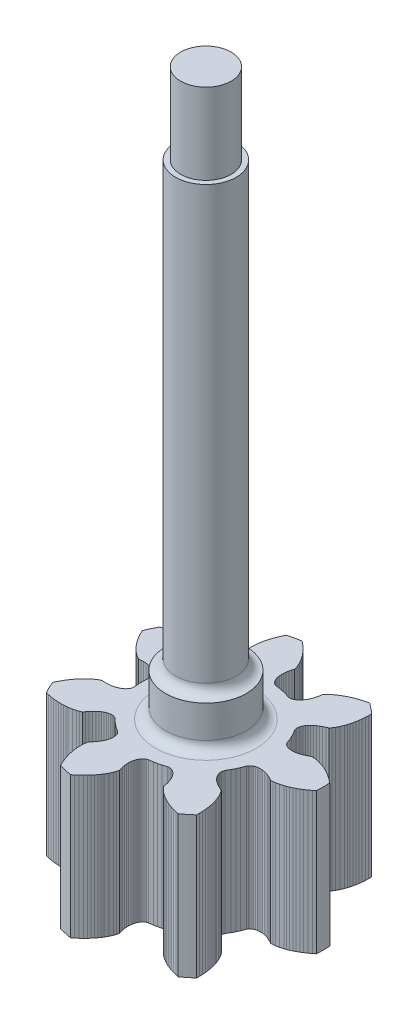
SolidWorks part; units mm, degrees
ref_plane "Front Plane" through (0, 0, 0) normal (0, 0, 1) x (1, 0, 0)
ref_plane "Top Plane" through (0, 0, 0) normal (0, 1, 0) x (1, 0, 0)
ref_plane "Right Plane" through (0, 0, 0) normal (1, 0, 0) x (0, 0, -1)
sketch "Sketch1" plane through (0, 0, 0) normal (0, 1, 0) x (1, 0, 0)
  circle A0 centre (0, 0) radius 2
  dimension "D1" = 4
extrude "Boss-Extrude1" add sketch "Sketch1" along normal blind 2.1
sketch "Sketch2" plane through (0, 2.1, 0) normal (0, 1, 0) x (1, 0, 0)
  circle A0 centre (0, 0) radius 1.5
  dimension "D1" = 3
extrude "Boss-Extrude3" add sketch "Sketch2" along normal blind 25.9
sketch "Sketch4" plane through (0, 0, 0) normal (0, -1, 0) x (1, 0, 0)
  line L420 (-1.6777, -5.4575) -> (-1.7402, -5.3144)
  line L421 (-1.7402, -5.3144) -> (-1.7939, -5.1757)
  line L422 (-1.7939, -5.1757) -> (-1.8392, -5.0423)
  line L423 (-1.8392, -5.0423) -> (-1.8764, -4.916)
  line L424 (-1.8764, -4.916) -> (-1.9071, -4.7932)
  line L425 (-1.9071, -4.7932) -> (-1.9311, -4.676)
  line L426 (-1.9311, -4.676) -> (-1.9488, -4.5668)
  line L427 (-1.9488, -4.5668) -> (-1.961, -4.464)
  line L428 (-1.961, -4.464) -> (-1.9715, -4.2798)
  line L429 (-1.9715, -4.2798) -> (-1.9674, -4.1246)
  line L430 (-1.9674, -4.1246) -> (-1.9537, -4.0009)
  line L431 (-1.9537, -4.0009) -> (-1.9303, -3.8867)
  line L432 (-1.9303, -3.8867) -> (-1.8594, -3.8097)
  line L433 (-1.8594, -3.8097) -> (-1.7784, -3.7125)
  line L434 (-1.7784, -3.7125) -> (-1.7087, -3.6155)
  line L435 (-1.7087, -3.6155) -> (-1.6501, -3.5195)
  line L436 (-1.6501, -3.5195) -> (-1.6023, -3.4251)
  line L437 (-1.6023, -3.4251) -> (-1.5652, -3.3333)
  line L438 (-1.5652, -3.3333) -> (-1.5384, -3.2446)
  line L439 (-1.5384, -3.2446) -> (-1.5215, -3.1597)
  line L440 (-1.5215, -3.1597) -> (-1.5143, -3.0795)
  line L441 (-1.5143, -3.0795) -> (-1.5162, -3.0043)
  line L442 (-1.5162, -3.0043) -> (-1.5269, -2.935)
  line L443 (-1.5269, -2.935) -> (-1.5457, -2.8721)
  line L444 (-1.5457, -2.8721) -> (-1.5723, -2.8162)
  line L445 (-1.5723, -2.8162) -> (-1.606, -2.7677)
  line L446 (-1.606, -2.7677) -> (-1.6572, -2.7183)
  line L447 (-1.6572, -2.7183) -> (-1.8447, -2.5928)
  line L448 (-1.8447, -2.5928) -> (-1.984, -2.4878)
  line L449 (-1.984, -2.4878) -> (-2.1173, -2.3754)
  line L450 (-2.1173, -2.3754) -> (-2.2814, -2.2205)
  line L451 (-2.2814, -2.2205) -> (-2.341, -2.1815)
  line L452 (-2.341, -2.1815) -> (-2.3957, -2.1595)
  line L453 (-2.3957, -2.1595) -> (-2.4562, -2.146)
  line L454 (-2.4562, -2.146) -> (-2.5217, -2.1417)
  line L455 (-2.5217, -2.1417) -> (-2.5917, -2.1467)
  line L456 (-2.5917, -2.1467) -> (-2.6653, -2.1615)
  line L457 (-2.6653, -2.1615) -> (-2.742, -2.1865)
  line L458 (-2.742, -2.1865) -> (-2.8209, -2.2218)
  line L459 (-2.8209, -2.2218) -> (-2.9014, -2.2676)
  line L460 (-2.9014, -2.2676) -> (-2.9827, -2.3243)
  line L461 (-2.9827, -2.3243) -> (-3.0641, -2.3918)
  line L462 (-3.0641, -2.3918) -> (-3.1447, -2.4703)
  line L463 (-3.1447, -2.4703) -> (-3.2237, -2.5599)
  line L464 (-3.2237, -2.5599) -> (-3.3005, -2.6605)
  line L465 (-3.3005, -2.6605) -> (-3.3598, -2.7467)
  line L466 (-3.3598, -2.7467) -> (-3.4659, -2.795)
  line L467 (-3.4659, -2.795) -> (-3.5835, -2.8358)
  line L468 (-3.5835, -2.8358) -> (-3.7338, -2.8744)
  line L469 (-3.7338, -2.8744) -> (-3.9158, -2.9052)
  line L470 (-3.9158, -2.9052) -> (-4.0187, -2.9161)
  line L471 (-4.0187, -2.9161) -> (-4.1291, -2.9232)
  line L472 (-4.1291, -2.9232) -> (-4.2487, -2.9258)
  line L473 (-4.2487, -2.9258) -> (-4.3752, -2.9233)
  line L474 (-4.3752, -2.9233) -> (-4.5067, -2.9151)
  line L475 (-4.5067, -2.9151) -> (-4.6468, -2.9006)
  line L476 (-4.6468, -2.9006) -> (-4.794, -2.8791)
  line L477 (-4.794, -2.8791) -> (-4.9474, -2.85)
  line L478 (-4.9474, -2.85) -> (-5.0902, -2.8167)
  line L479 (-5.3759, -2.2235) -> (-5.3129, -2.0911)
  line L480 (-5.3129, -2.0911) -> (-5.2399, -1.953)
  line L481 (-5.2399, -1.953) -> (-5.165, -1.8245)
  line L482 (-5.165, -1.8245) -> (-5.089, -1.7059)
  line L483 (-5.089, -1.7059) -> (-5.0134, -1.5981)
  line L484 (-5.0134, -1.5981) -> (-4.9365, -1.4976)
  line L485 (-4.9365, -1.4976) -> (-4.8599, -1.4057)
  line L486 (-4.8599, -1.4057) -> (-4.7855, -1.3238)
  line L487 (-4.7855, -1.3238) -> (-4.7128, -1.2502)
  line L488 (-4.7128, -1.2502) -> (-4.5753, -1.1271)
  line L489 (-4.5753, -1.1271) -> (-4.4514, -1.0336)
  line L490 (-4.4514, -1.0336) -> (-4.3462, -0.9671)
  line L491 (-4.3462, -0.9671) -> (-4.2422, -0.9142)
  line L492 (-4.2422, -0.9142) -> (-4.1379, -0.9217)
  line L493 (-4.1379, -0.9217) -> (-4.0114, -0.9244)
  line L494 (-4.0114, -0.9244) -> (-3.8921, -0.9184)
  line L495 (-3.8921, -0.9184) -> (-3.7804, -0.9043)
  line L496 (-3.7804, -0.9043) -> (-3.6769, -0.8828)
  line L497 (-3.6769, -0.8828) -> (-3.5819, -0.8546)
  line L498 (-3.5819, -0.8546) -> (-3.4959, -0.8203)
  line L499 (-3.4959, -0.8203) -> (-3.4191, -0.7805)
  line L500 (-3.4191, -0.7805) -> (-3.3518, -0.7361)
  line L501 (-3.3518, -0.7361) -> (-3.2942, -0.6878)
  line L502 (-3.2942, -0.6878) -> (-3.2467, -0.6363)
  line L503 (-3.2467, -0.6363) -> (-3.2093, -0.5823)
  line L504 (-3.2093, -0.5823) -> (-3.1821, -0.5267)
  line L505 (-3.1821, -0.5267) -> (-3.1652, -0.4701)
  line L506 (-3.1652, -0.4701) -> (-3.1585, -0.3992)
  line L507 (-3.1585, -0.3992) -> (-3.1773, -0.1744)
  line L508 (-3.1773, -0.1744) -> (-3.1821, 0)
  line L509 (-3.1821, 0) -> (-3.1773, 0.1743)
  line L510 (-3.1773, 0.1743) -> (-3.1585, 0.3991)
  line L511 (-3.1585, 0.3991) -> (-3.1652, 0.47)
  line L512 (-3.1652, 0.47) -> (-3.1821, 0.5266)
  line L513 (-3.1821, 0.5266) -> (-3.2093, 0.5822)
  line L514 (-3.2093, 0.5822) -> (-3.2467, 0.6362)
  line L515 (-3.2467, 0.6362) -> (-3.2942, 0.6877)
  line L516 (-3.2942, 0.6877) -> (-3.3518, 0.7361)
  line L517 (-3.3518, 0.7361) -> (-3.4191, 0.7805)
  line L518 (-3.4191, 0.7805) -> (-3.4959, 0.8202)
  line L519 (-3.4959, 0.8202) -> (-3.5819, 0.8545)
  line L520 (-3.5819, 0.8545) -> (-3.6769, 0.8828)
  line L521 (-3.6769, 0.8828) -> (-3.7804, 0.9043)
  line L522 (-3.7804, 0.9043) -> (-3.8921, 0.9183)
  line L523 (-3.8921, 0.9183) -> (-4.0114, 0.9243)
  line L524 (-4.0114, 0.9243) -> (-4.1379, 0.9216)
  line L525 (-4.1379, 0.9216) -> (-4.2422, 0.9142)
  line L526 (-4.2422, 0.9142) -> (-4.3462, 0.967)
  line L527 (-4.3462, 0.967) -> (-4.4514, 1.0335)
  line L528 (-4.4514, 1.0335) -> (-4.5753, 1.127)
  line L529 (-4.5753, 1.127) -> (-4.7128, 1.2501)
  line L530 (-4.7128, 1.2501) -> (-4.7855, 1.3238)
  line L531 (-4.7855, 1.3238) -> (-4.8599, 1.4056)
  line L532 (-4.8599, 1.4056) -> (-4.9365, 1.4975)
  line L533 (-4.9365, 1.4975) -> (-5.0134, 1.598)
  line L534 (-5.0134, 1.598) -> (-5.089, 1.7059)
  line L535 (-5.089, 1.7059) -> (-5.165, 1.8244)
  line L536 (-5.165, 1.8244) -> (-5.2399, 1.9529)
  line L537 (-5.2399, 1.9529) -> (-5.3129, 2.0911)
  line L538 (-5.3129, 2.0911) -> (-5.3759, 2.2234)
  line L539 (-5.0902, 2.8167) -> (-4.9474, 2.8499)
  line L540 (-4.9474, 2.8499) -> (-4.794, 2.879)
  line L541 (-4.794, 2.879) -> (-4.6468, 2.9005)
  line L542 (-4.6468, 2.9005) -> (-4.5067, 2.9151)
  line L543 (-4.5067, 2.9151) -> (-4.3752, 2.9232)
  line L544 (-4.3752, 2.9232) -> (-4.2487, 2.9257)
  line L545 (-4.2487, 2.9257) -> (-4.1291, 2.9231)
  line L546 (-4.1291, 2.9231) -> (-4.0187, 2.916)
  line L547 (-4.0187, 2.916) -> (-3.9158, 2.9051)
  line L548 (-3.9158, 2.9051) -> (-3.7338, 2.8743)
  line L549 (-3.7338, 2.8743) -> (-3.5835, 2.8358)
  line L550 (-3.5835, 2.8358) -> (-3.4659, 2.7949)
  line L551 (-3.4659, 2.7949) -> (-3.3598, 2.7466)
  line L552 (-3.3598, 2.7466) -> (-3.3005, 2.6604)
  line L553 (-3.3005, 2.6604) -> (-3.2237, 2.5598)
  line L554 (-3.2237, 2.5598) -> (-3.1447, 2.4703)
  line L555 (-3.1447, 2.4703) -> (-3.0641, 2.3918)
  line L556 (-3.0641, 2.3918) -> (-2.9827, 2.3242)
  line L557 (-2.9827, 2.3242) -> (-2.9014, 2.2676)
  line L558 (-2.9014, 2.2676) -> (-2.8209, 2.2217)
  line L559 (-2.8209, 2.2217) -> (-2.742, 2.1864)
  line L560 (-2.742, 2.1864) -> (-2.6653, 2.1615)
  line L561 (-2.6653, 2.1615) -> (-2.5917, 2.1466)
  line L562 (-2.5917, 2.1466) -> (-2.5217, 2.1416)
  line L563 (-2.5217, 2.1416) -> (-2.4562, 2.146)
  line L564 (-2.4562, 2.146) -> (-2.3957, 2.1594)
  line L565 (-2.3957, 2.1594) -> (-2.341, 2.1815)
  line L566 (-2.341, 2.1815) -> (-2.2814, 2.2205)
  line L567 (-2.2814, 2.2205) -> (-2.1173, 2.3753)
  line L568 (-2.1173, 2.3753) -> (-1.984, 2.4878)
  line L569 (-1.984, 2.4878) -> (-1.8447, 2.5927)
  line L570 (-1.8447, 2.5927) -> (-1.6572, 2.7182)
  line L571 (-1.6572, 2.7182) -> (-1.606, 2.7676)
  line L572 (-1.606, 2.7676) -> (-1.5723, 2.8161)
  line L573 (-1.5723, 2.8161) -> (-1.5457, 2.8721)
  line L574 (-1.5457, 2.8721) -> (-1.5269, 2.935)
  line L575 (-1.5269, 2.935) -> (-1.5162, 3.0043)
  line L576 (-1.5162, 3.0043) -> (-1.5143, 3.0794)
  line L577 (-1.5143, 3.0794) -> (-1.5215, 3.1597)
  line L578 (-1.5215, 3.1597) -> (-1.5384, 3.2445)
  line L579 (-1.5384, 3.2445) -> (-1.5652, 3.3332)
  line L580 (-1.5652, 3.3332) -> (-1.6023, 3.4251)
  line L581 (-1.6023, 3.4251) -> (-1.6501, 3.5194)
  line L582 (-1.6501, 3.5194) -> (-1.7087, 3.6154)
  line L583 (-1.7087, 3.6154) -> (-1.7784, 3.7125)
  line L584 (-1.7784, 3.7125) -> (-1.8594, 3.8097)
  line L585 (-1.8594, 3.8097) -> (-1.9303, 3.8866)
  line L586 (-1.9303, 3.8866) -> (-1.9537, 4.0009)
  line L587 (-1.9537, 4.0009) -> (-1.9674, 4.1246)
  line L588 (-1.9674, 4.1246) -> (-1.9715, 4.2797)
  line L589 (-1.9715, 4.2797) -> (-1.961, 4.464)
  line L590 (-1.961, 4.464) -> (-1.9488, 4.5668)
  line L591 (-1.9488, 4.5668) -> (-1.9311, 4.6759)
  line L592 (-1.9311, 4.6759) -> (-1.9071, 4.7932)
  line L593 (-1.9071, 4.7932) -> (-1.8764, 4.9159)
  line L594 (-1.8764, 4.9159) -> (-1.8392, 5.0423)
  line L595 (-1.8392, 5.0423) -> (-1.7939, 5.1756)
  line L596 (-1.7939, 5.1756) -> (-1.7402, 5.3143)
  line L597 (-1.7402, 5.3143) -> (-1.6777, 5.4575)
  line L598 (-1.6777, 5.4575) -> (-1.6135, 5.5893)
  line L599 (-0.9715, 5.7358) -> (-0.8565, 5.6449)
  line L600 (-0.8565, 5.6449) -> (-0.7381, 5.543)
  line L601 (-0.7381, 5.543) -> (-0.6295, 5.4414)
  line L602 (-0.6295, 5.4414) -> (-0.5308, 5.3409)
  line L603 (-0.5308, 5.3409) -> (-0.4425, 5.2432)
  line L604 (-0.4425, 5.2432) -> (-0.3616, 5.1459)
  line L605 (-0.3616, 5.1459) -> (-0.2891, 5.0507)
  line L606 (-0.2891, 5.0507) -> (-0.2258, 4.96)
  line L607 (-0.2258, 4.96) -> (-0.1702, 4.8727)
  line L608 (-0.1702, 4.8727) -> (-0.0808, 4.7113)
  line L609 (-0.0808, 4.7113) -> (-0.0172, 4.5697)
  line L610 (-0.0172, 4.5697) -> (0.0242, 4.4523)
  line L611 (0.0242, 4.4523) -> (0.0526, 4.3392)
  line L612 (0.0526, 4.3392) -> (0.0222, 4.2391)
  line L613 (0.0222, 4.2391) -> (-0.0086, 4.1164)
  line L614 (-0.0086, 4.1164) -> (-0.0293, 3.9987)
  line L615 (-0.0293, 3.9987) -> (-0.0405, 3.8868)
  line L616 (-0.0405, 3.8868) -> (-0.0426, 3.7811)
  line L617 (-0.0426, 3.7811) -> (-0.0362, 3.6822)
  line L618 (-0.0362, 3.6822) -> (-0.0218, 3.5907)
  line L619 (-0.0218, 3.5907) -> (-0.0002, 3.5069)
  line L620 (-0.0002, 3.5069) -> (0.0281, 3.4314)
  line L621 (0.0281, 3.4314) -> (0.0624, 3.3646)
  line L622 (0.0624, 3.3646) -> (0.1021, 3.3068)
  line L623 (0.1021, 3.3068) -> (0.1464, 3.2583)
  line L624 (0.1464, 3.2583) -> (0.1946, 3.2194)
  line L625 (0.1946, 3.2194) -> (0.246, 3.1903)
  line L626 (0.246, 3.1903) -> (0.3136, 3.1681)
  line L627 (0.3136, 3.1681) -> (0.537, 3.1363)
  line L628 (0.537, 3.1363) -> (0.708, 3.1022)
  line L629 (0.708, 3.1022) -> (0.8769, 3.0588)
  line L630 (0.8769, 3.0588) -> (1.0919, 2.9904)
  line L631 (1.0919, 2.9904) -> (1.1625, 2.9811)
  line L632 (1.1625, 2.9811) -> (1.2214, 2.985)
  line L633 (1.2214, 2.985) -> (1.2817, 2.9991)
  line L634 (1.2817, 2.9991) -> (1.3427, 3.0236)
  line L635 (1.3427, 3.0236) -> (1.4035, 3.0585)
  line L636 (1.4035, 3.0585) -> (1.4634, 3.1038)
  line L637 (1.4634, 3.1038) -> (1.5217, 3.1596)
  line L638 (1.5217, 3.1596) -> (1.5775, 3.2256)
  line L639 (1.5775, 3.2256) -> (1.6301, 3.3019)
  line L640 (1.6301, 3.3019) -> (1.6788, 3.3882)
  line L641 (1.6788, 3.3882) -> (1.7228, 3.4843)
  line L642 (1.7228, 3.4843) -> (1.7613, 3.59)
  line L643 (1.7613, 3.59) -> (1.7937, 3.705)
  line L644 (1.7937, 3.705) -> (1.8192, 3.829)
  line L645 (1.8192, 3.829) -> (1.8352, 3.9324)
  line L646 (1.8352, 3.9324) -> (1.9099, 4.0219)
  line L647 (1.9099, 4.0219) -> (1.9981, 4.1097)
  line L648 (1.9981, 4.1097) -> (2.1168, 4.2097)
  line L649 (2.1168, 4.2097) -> (2.2674, 4.3164)
  line L650 (2.2674, 4.3164) -> (2.3554, 4.3709)
  line L651 (2.3554, 4.3709) -> (2.4518, 4.4251)
  line L652 (2.4518, 4.4251) -> (2.5584, 4.4794)
  line L653 (2.5584, 4.4794) -> (2.6735, 4.532)
  line L654 (2.6735, 4.532) -> (2.7955, 4.5817)
  line L655 (2.7955, 4.5817) -> (2.928, 4.6294)
  line L656 (2.928, 4.6294) -> (3.0699, 4.6739)
  line L657 (3.0699, 4.6739) -> (3.2208, 4.7143)
  line L658 (3.2208, 4.7143) -> (3.3639, 4.7463)
  line L659 (3.8787, 4.3357) -> (3.8793, 4.1891)
  line L660 (3.8793, 4.1891) -> (3.8735, 4.033)
  line L661 (3.8735, 4.033) -> (3.8618, 3.8847)
  line L662 (3.8618, 3.8847) -> (3.8448, 3.7449)
  line L663 (3.8448, 3.7449) -> (3.8234, 3.615)
  line L664 (3.8234, 3.615) -> (3.7978, 3.4911)
  line L665 (3.7978, 3.4911) -> (3.7686, 3.375)
  line L666 (3.7686, 3.375) -> (3.7371, 3.269)
  line L667 (3.7371, 3.269) -> (3.7036, 3.1711)
  line L668 (3.7036, 3.1711) -> (3.6331, 3.0005)
  line L669 (3.6331, 3.0005) -> (3.562, 2.8625)
  line L670 (3.562, 2.8625) -> (3.4961, 2.757)
  line L671 (3.4961, 2.757) -> (3.4253, 2.6643)
  line L672 (3.4253, 2.6643) -> (3.3281, 2.6257)
  line L673 (3.3281, 2.6257) -> (3.213, 2.5732)
  line L674 (3.213, 2.5732) -> (3.1081, 2.516)
  line L675 (3.1081, 2.516) -> (3.0136, 2.4549)
  line L676 (3.0136, 2.4549) -> (2.9296, 2.3907)
  line L677 (2.9296, 2.3907) -> (2.8563, 2.324)
  line L678 (2.8563, 2.324) -> (2.7937, 2.2557)
  line L679 (2.7937, 2.2557) -> (2.7417, 2.1866)
  line L680 (2.7417, 2.1866) -> (2.7003, 2.1174)
  line L681 (2.7003, 2.1174) -> (2.6695, 2.0489)
  line L682 (2.6695, 2.0489) -> (2.649, 1.9819)
  line L683 (2.649, 1.9819) -> (2.6387, 1.917)
  line L684 (2.6387, 1.917) -> (2.6383, 1.8551)
  line L685 (2.6383, 1.8551) -> (2.6476, 1.7967)
  line L686 (2.6476, 1.7967) -> (2.6724, 1.73)
  line L687 (2.6724, 1.73) -> (2.7869, 1.5356)
  line L688 (2.7869, 1.5356) -> (2.8668, 1.3806)
  line L689 (2.8668, 1.3806) -> (2.9382, 1.2215)
  line L690 (2.9382, 1.2215) -> (3.0188, 1.0107)
  line L691 (3.0188, 1.0107) -> (3.0555, 0.9498)
  line L692 (3.0555, 0.9498) -> (3.0953, 0.9061)
  line L693 (3.0953, 0.9061) -> (3.144, 0.8678)
  line L694 (3.144, 0.8678) -> (3.2011, 0.8354)
  line L695 (3.2011, 0.8354) -> (3.2663, 0.8096)
  line L696 (3.2663, 0.8096) -> (3.3391, 0.791)
  line L697 (3.3391, 0.791) -> (3.419, 0.7802)
  line L698 (3.419, 0.7802) -> (3.5054, 0.7777)
  line L699 (3.5054, 0.7777) -> (3.5979, 0.7842)
  line L700 (3.5979, 0.7842) -> (3.6957, 0.7999)
  line L701 (3.6957, 0.7999) -> (3.7983, 0.8255)
  line L702 (3.7983, 0.8255) -> (3.905, 0.8612)
  line L703 (3.905, 0.8612) -> (4.0151, 0.9076)
  line L704 (4.0151, 0.9076) -> (4.1279, 0.9649)
  line L705 (4.1279, 0.9649) -> (4.2187, 1.0169)
  line L706 (4.2187, 1.0169) -> (4.3353, 1.0144)
  line L707 (4.3353, 1.0144) -> (4.4589, 1.0001)
  line L708 (4.4589, 1.0001) -> (4.6111, 0.9696)
  line L709 (4.6111, 0.9696) -> (4.7884, 0.9184)
  line L710 (4.7884, 0.9184) -> (4.8859, 0.8836)
  line L711 (4.8859, 0.8836) -> (4.9884, 0.8421)
  line L712 (4.9884, 0.8421) -> (5.0973, 0.7926)
  line L713 (5.0973, 0.7926) -> (5.2102, 0.7354)
  line L714 (5.2102, 0.7354) -> (5.3251, 0.671)
  line L715 (5.3251, 0.671) -> (5.445, 0.5972)
  line L716 (5.445, 0.5972) -> (5.5683, 0.5139)
  line L717 (5.5683, 0.5139) -> (5.6939, 0.4211)
  line L718 (5.6939, 0.4211) -> (5.8081, 0.3292)
  line L719 (5.8081, -0.3293) -> (5.6939, -0.4212)
  line L720 (5.6939, -0.4212) -> (5.5683, -0.514)
  line L721 (5.5683, -0.514) -> (5.445, -0.5972)
  line L722 (5.445, -0.5972) -> (5.3251, -0.6711)
  line L723 (5.3251, -0.6711) -> (5.2102, -0.7354)
  line L724 (5.2102, -0.7354) -> (5.0973, -0.7926)
  line L725 (5.0973, -0.7926) -> (4.9884, -0.8421)
  line L726 (4.9884, -0.8421) -> (4.8859, -0.8837)
  line L727 (4.8859, -0.8837) -> (4.7884, -0.9185)
  line L728 (4.7884, -0.9185) -> (4.6111, -0.9697)
  line L729 (4.6111, -0.9697) -> (4.4589, -1.0002)
  line L730 (4.4589, -1.0002) -> (4.3353, -1.0144)
  line L731 (4.3353, -1.0144) -> (4.2187, -1.017)
  line L732 (4.2187, -1.017) -> (4.1279, -0.965)
  line L733 (4.1279, -0.965) -> (4.0151, -0.9077)
  line L734 (4.0151, -0.9077) -> (3.905, -0.8613)
  line L735 (3.905, -0.8613) -> (3.7983, -0.8255)
  line L736 (3.7983, -0.8255) -> (3.6957, -0.8)
  line L737 (3.6957, -0.8) -> (3.5979, -0.7842)
  line L738 (3.5979, -0.7842) -> (3.5054, -0.7778)
  line L739 (3.5054, -0.7778) -> (3.419, -0.7803)
  line L740 (3.419, -0.7803) -> (3.3391, -0.7911)
  line L741 (3.3391, -0.7911) -> (3.2663, -0.8097)
  line L742 (3.2663, -0.8097) -> (3.2011, -0.8354)
  line L743 (3.2011, -0.8354) -> (3.144, -0.8678)
  line L744 (3.144, -0.8678) -> (3.0953, -0.9062)
  line L745 (3.0953, -0.9062) -> (3.0555, -0.9498)
  line L746 (3.0555, -0.9498) -> (3.0188, -1.0108)
  line L747 (3.0188, -1.0108) -> (2.9382, -1.2215)
  line L748 (2.9382, -1.2215) -> (2.8668, -1.3806)
  line L749 (2.8668, -1.3806) -> (2.7869, -1.5356)
  line L750 (2.7869, -1.5356) -> (2.6724, -1.7301)
  line L751 (2.6724, -1.7301) -> (2.6476, -1.7968)
  line L752 (2.6476, -1.7968) -> (2.6383, -1.8551)
  line L753 (2.6383, -1.8551) -> (2.6387, -1.9171)
  line L754 (2.6387, -1.9171) -> (2.649, -1.9819)
  line L755 (2.649, -1.9819) -> (2.6695, -2.049)
  line L756 (2.6695, -2.049) -> (2.7003, -2.1175)
  line L757 (2.7003, -2.1175) -> (2.7417, -2.1867)
  line L758 (2.7417, -2.1867) -> (2.7937, -2.2558)
  line L759 (2.7937, -2.2558) -> (2.8563, -2.3241)
  line L760 (2.8563, -2.3241) -> (2.9296, -2.3907)
  line L761 (2.9296, -2.3907) -> (3.0136, -2.455)
  line L762 (3.0136, -2.455) -> (3.1081, -2.5161)
  line L763 (3.1081, -2.5161) -> (3.213, -2.5733)
  line L764 (3.213, -2.5733) -> (3.3281, -2.6257)
  line L765 (3.3281, -2.6257) -> (3.4253, -2.6643)
  line L766 (3.4253, -2.6643) -> (3.4961, -2.757)
  line L767 (3.4961, -2.757) -> (3.562, -2.8626)
  line L768 (3.562, -2.8626) -> (3.6331, -3.0006)
  line L769 (3.6331, -3.0006) -> (3.7036, -3.1711)
  line L770 (3.7036, -3.1711) -> (3.7371, -3.2691)
  line L771 (3.7371, -3.2691) -> (3.7686, -3.3751)
  line L772 (3.7686, -3.3751) -> (3.7978, -3.4911)
  line L773 (3.7978, -3.4911) -> (3.8234, -3.615)
  line L774 (3.8234, -3.615) -> (3.8448, -3.745)
  line L775 (3.8448, -3.745) -> (3.8618, -3.8848)
  line L776 (3.8618, -3.8848) -> (3.8735, -4.0331)
  line L777 (3.8735, -4.0331) -> (3.8793, -4.1892)
  line L778 (3.8793, -4.1892) -> (3.8787, -4.3358)
  line L779 (3.3639, -4.7463) -> (3.2208, -4.7143)
  line L780 (3.2208, -4.7143) -> (3.0699, -4.6739)
  line L781 (3.0699, -4.6739) -> (2.928, -4.6295)
  line L782 (2.928, -4.6295) -> (2.7955, -4.5818)
  line L783 (2.7955, -4.5818) -> (2.6735, -4.5321)
  line L784 (2.6735, -4.5321) -> (2.5584, -4.4795)
  line L785 (2.5584, -4.4795) -> (2.4518, -4.4252)
  line L786 (2.4518, -4.4252) -> (2.3554, -4.3709)
  line L787 (2.3554, -4.3709) -> (2.2674, -4.3164)
  line L788 (2.2674, -4.3164) -> (2.1168, -4.2097)
  line L789 (2.1168, -4.2097) -> (1.9981, -4.1098)
  line L790 (1.9981, -4.1098) -> (1.9099, -4.022)
  line L791 (1.9099, -4.022) -> (1.8352, -3.9324)
  line L792 (1.8352, -3.9324) -> (1.8192, -3.829)
  line L793 (1.8192, -3.829) -> (1.7937, -3.7051)
  line L794 (1.7937, -3.7051) -> (1.7613, -3.5901)
  line L795 (1.7613, -3.5901) -> (1.7228, -3.4844)
  line L796 (1.7228, -3.4844) -> (1.6788, -3.3883)
  line L797 (1.6788, -3.3883) -> (1.6301, -3.3019)
  line L798 (1.6301, -3.3019) -> (1.5775, -3.2257)
  line L799 (1.5775, -3.2257) -> (1.5217, -3.1596)
  line L800 (1.5217, -3.1596) -> (1.4634, -3.1039)
  line L801 (1.4634, -3.1039) -> (1.4035, -3.0586)
  line L802 (1.4035, -3.0586) -> (1.3427, -3.0237)
  line L803 (1.3427, -3.0237) -> (1.2817, -2.9992)
  line L804 (1.2817, -2.9992) -> (1.2214, -2.9851)
  line L805 (1.2214, -2.9851) -> (1.1625, -2.9812)
  line L806 (1.1625, -2.9812) -> (1.0919, -2.9905)
  line L807 (1.0919, -2.9905) -> (0.8769, -3.0588)
  line L808 (0.8769, -3.0588) -> (0.708, -3.1023)
  line L809 (0.708, -3.1023) -> (0.537, -3.1364)
  line L810 (0.537, -3.1364) -> (0.3136, -3.1681)
  line L811 (0.3136, -3.1681) -> (0.246, -3.1904)
  line L812 (0.246, -3.1904) -> (0.1946, -3.2194)
  line L813 (0.1946, -3.2194) -> (0.1464, -3.2583)
  line L814 (0.1464, -3.2583) -> (0.1021, -3.3068)
  line L815 (0.1021, -3.3068) -> (0.0624, -3.3647)
  line L816 (0.0624, -3.3647) -> (0.0281, -3.4315)
  line L817 (0.0281, -3.4315) -> (-0.0002, -3.507)
  line L818 (-0.0002, -3.507) -> (-0.0218, -3.5907)
  line L819 (-0.0218, -3.5907) -> (-0.0362, -3.6823)
  line L820 (-0.0362, -3.6823) -> (-0.0426, -3.7811)
  line L821 (-0.0426, -3.7811) -> (-0.0405, -3.8868)
  line L822 (-0.0405, -3.8868) -> (-0.0293, -3.9988)
  line L823 (-0.0293, -3.9988) -> (-0.0086, -4.1165)
  line L824 (-0.0086, -4.1165) -> (0.0222, -4.2392)
  line L825 (0.0222, -4.2392) -> (0.0526, -4.3393)
  line L826 (0.0526, -4.3393) -> (0.0242, -4.4524)
  line L827 (0.0242, -4.4524) -> (-0.0172, -4.5698)
  line L828 (-0.0172, -4.5698) -> (-0.0808, -4.7113)
  line L829 (-0.0808, -4.7113) -> (-0.1702, -4.8728)
  line L830 (-0.1702, -4.8728) -> (-0.2258, -4.9601)
  line L831 (-0.2258, -4.9601) -> (-0.2891, -5.0508)
  line L832 (-0.2891, -5.0508) -> (-0.3616, -5.146)
  line L833 (-0.3616, -5.146) -> (-0.4425, -5.2433)
  line L834 (-0.4425, -5.2433) -> (-0.5308, -5.341)
  line L835 (-0.5308, -5.341) -> (-0.6295, -5.4414)
  line L836 (-0.6295, -5.4414) -> (-0.7381, -5.5431)
  line L837 (-0.7381, -5.5431) -> (-0.8565, -5.645)
  line L838 (-0.8565, -5.645) -> (-0.9715, -5.7359)
  line L839 (-1.6135, -5.5894) -> (-1.6777, -5.4575)
  arc A7 (-5.3759, -2.2235) -> (-5.0902, -2.8167) centre (0, 0) ccw
  arc A8 (-5.0902, 2.8167) -> (-5.3759, 2.2234) centre (0, -0.0001) ccw
  arc A9 (-0.9715, 5.7358) -> (-1.6135, 5.5893) centre (0, -0.0001) ccw
  arc A10 (3.8787, 4.3357) -> (3.3639, 4.7463) centre (-0.0001, -0.0001) ccw
  arc A11 (5.8081, -0.3293) -> (5.8081, 0.3292) centre (-0.0001, 0) ccw
  arc A12 (3.3639, -4.7463) -> (3.8787, -4.3358) centre (-0.0001, 0) ccw
  arc A13 (-1.6135, -5.5894) -> (-0.9715, -5.7359) centre (0, 0) ccw
extrude "Boss-Extrude4" add sketch "Sketch4" along normal blind 7
sketch "Sketch3" plane through (0, 0, 0) normal (0, -1, 0) x (1, 0, 0)
  circle A0 centre (0, 0) radius 1.1
  circle A1 centre (0, 0) radius 0.75
  dimension "D1" = 2.2
  dimension "D2" = 1.5
extrude "Cut-Extrude2" [suppressed] cut sketch "Sketch3" along normal through all contours A0 A1 | A1
fillet "Fillet1" radius 0.5 2 edges at (0, 2.1, 1.5) (0, 0, -2)
chamfer "Chamfer1" [suppressed] distance 0.4 angle 45
ref_plane "Plane1" through (0, 2.1, 0) normal (0, -1, 0) x (-1, 0, 0)
ref_plane "Plane for bottom of support plate" through (0, 8.1, 0) normal (0, -1, 0) x (-1, 0, 0)
sketch "Sketch5" plane through (0, 28, 0) normal (0, 1, 0) x (1, 0, 0)
  circle A0 centre (0, 0) radius 1.5
  circle A1 centre (0, 0) radius 1.5 construction
  circle A2 centre (0, 0) radius 1.25
  dimension "D1" = 0.25
extrude "Cut-Extrude3" cut sketch "Sketch5" against normal blind 4
ref_plane "Plane for end of coupler" through (0, 12.1, 0) normal (0, -1, 0) x (-1, 0, 0)
ref_plane "Plane for end of torque spline sleeve" through (0, 13.1, 0) normal (0, -1, 0) x (-1, 0, 0)
